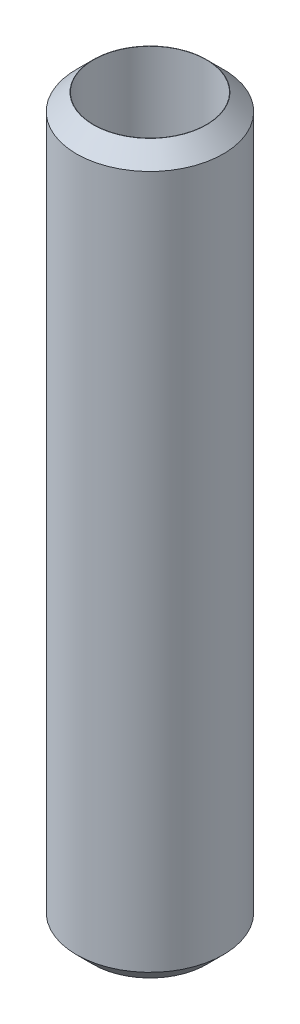
SolidWorks part; units mm, degrees
ref_plane "Front Plane" through (0, 0, 0) normal (0, 0, 1) x (1, 0, 0)
ref_plane "Top Plane" through (0, 0, 0) normal (0, 1, 0) x (1, 0, 0)
ref_plane "Right Plane" through (0, 0, 0) normal (1, 0, 0) x (0, 0, -1)
sketch "Sketch1" plane through (0, 0, 0) normal (0, 1, 0) x (1, 0, 0)
  circle A0 centre (0, 0) radius 17.5
  dimension "SHAFT_OD" = 35
extrude "Boss-Extrude1" add sketch "Sketch1" along normal blind 173.413
sketch "Sketch2" plane through (0, 0, 0) normal (0, 1, 0) x (1, 0, 0)
  circle A0 centre (0, 0) radius 13.4298
  dimension "BORE_D" = 26.8597
extrude "Cut-Extrude1" cut sketch "Sketch2" along normal through all
chamfer "Chamfer1" distance 4.0073 angle 45 2 edges at (0, 173.413, 17.5) (0, 0, 17.5)
